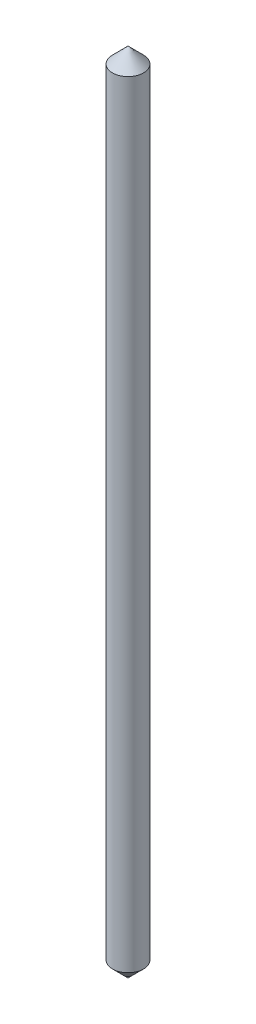
SolidWorks part; units mm, degrees
ref_plane "Alzado" through (0, 0, 0) normal (0, 0, 1) x (1, 0, 0)
ref_plane "Planta" through (0, 0, 0) normal (0, 1, 0) x (1, 0, 0)
ref_plane "Vista lateral" through (0, 0, 0) normal (1, 0, 0) x (0, 0, -1)
sketch "Croquis1" plane through (0, 0, 0) normal (0, 1, 0) x (1, 0, 0)
  circle A0 centre (0, 0) radius 5
  dimension "D1" = 10
extrude "Saliente-Extruir1" add sketch "Croquis1" along normal blind 250
ref_axis "Eje1" through (0, 250, 0) along (0, -1, 0)
sketch "Croquis2" plane through (0, 250, 0) normal (0, 1, 0) x (1, 0, 0)
  circle A0 centre (0, 0) radius 5
extrude "Saliente-Extruir2" add sketch "Croquis2" along normal blind 250 draft 45
sketch "Croquis3" plane through (0, 0, 0) normal (0, -1, 0) x (1, 0, 0)
  circle A0 centre (0, 0) radius 5
extrude "Saliente-Extruir3" add sketch "Croquis3" along normal blind 250 draft 45
